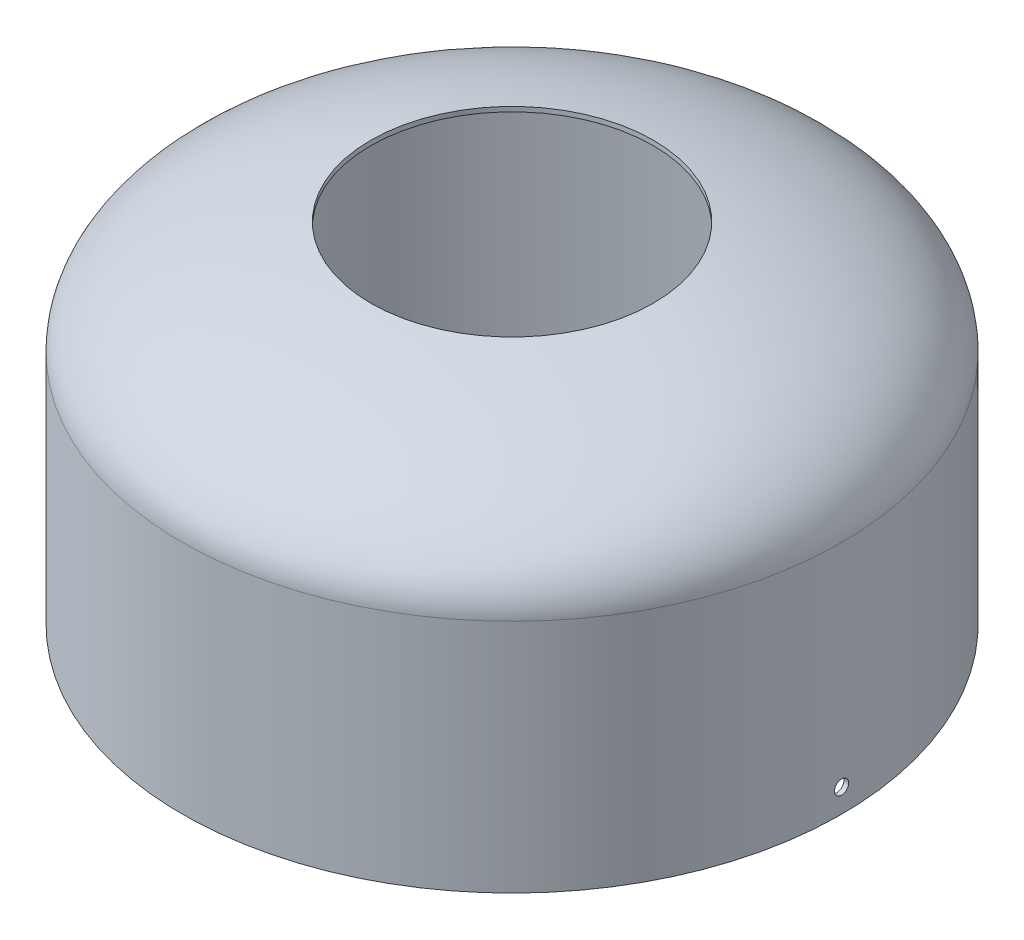
SolidWorks part; units mm, degrees
ref_plane "Front Plane" through (0, 0, 0) normal (0, 0, 1) x (1, 0, 0)
ref_plane "Top Plane" through (0, 0, 0) normal (0, 1, 0) x (1, 0, 0)
ref_plane "Right Plane" through (0, 0, 0) normal (1, 0, 0) x (0, 0, -1)
sketch "Sketch1" plane through (0, 0, 0) normal (0, 0, 1) x (1, 0, 0)
  line L0 (175.26, -127) -> (175.26, 0)
  line L1 (175.26, -127) -> (177.8, -127)
  line L2 (177.8, -127) -> (177.8, 0)
  line L3 (55, 0) -> (-55, 0) construction
  line L4 (76.2, 60.96) -> (76.2, 58.42)
  line L5 (0, -55) -> (0, 55) construction
  ellipse E0 centre (0, 0) end of major axis (177.8, 0) minor radius 67.4704 (177.8, 0) -> (76.2, 60.96) ccw
  ellipse E1 centre (0, 0) end of major axis (175.26, 0) minor radius 64.8725 (175.26, 0) -> (76.2, 58.42) ccw
  dimension "D1" = 177.8
  dimension "D2" = 2.54
  dimension "D3" = 127
  dimension "D4" = 2.54
  dimension "D5" = 76.2
  dimension "D6" = 58.42
ref_axis "Axis1" through (0, -109.728, 0) along (0, 1, 0)
revolve "Revolve1" add sketch "Sketch1" angle 360 about axis through (0, -109.728, 0) along (0, 1, 0)
sketch "Sketch2" plane through (0, 0, 0) normal (1, 0, 0) x (0, 0, -1)
  line L3 (0, -109.728) -> (0, 69.088) construction
  line L5 (195.58, 0) -> (-195.58, 0) construction
  circle A0 centre (0, -114.3) radius 3.81
  dimension "D1" = 7.62
  dimension "D2" = 114.3
extrude "Cut-Extrude1" cut sketch "Sketch2" against normal through all and the other way through all
ref_plane "chassi top reference plane" through (0, 0, 0) normal (0, 1, 0) x (1, 0, 0)
ref_axis "chassi horizontal" through (175.0037, -114.3, 0) along (1, 0, 0)
